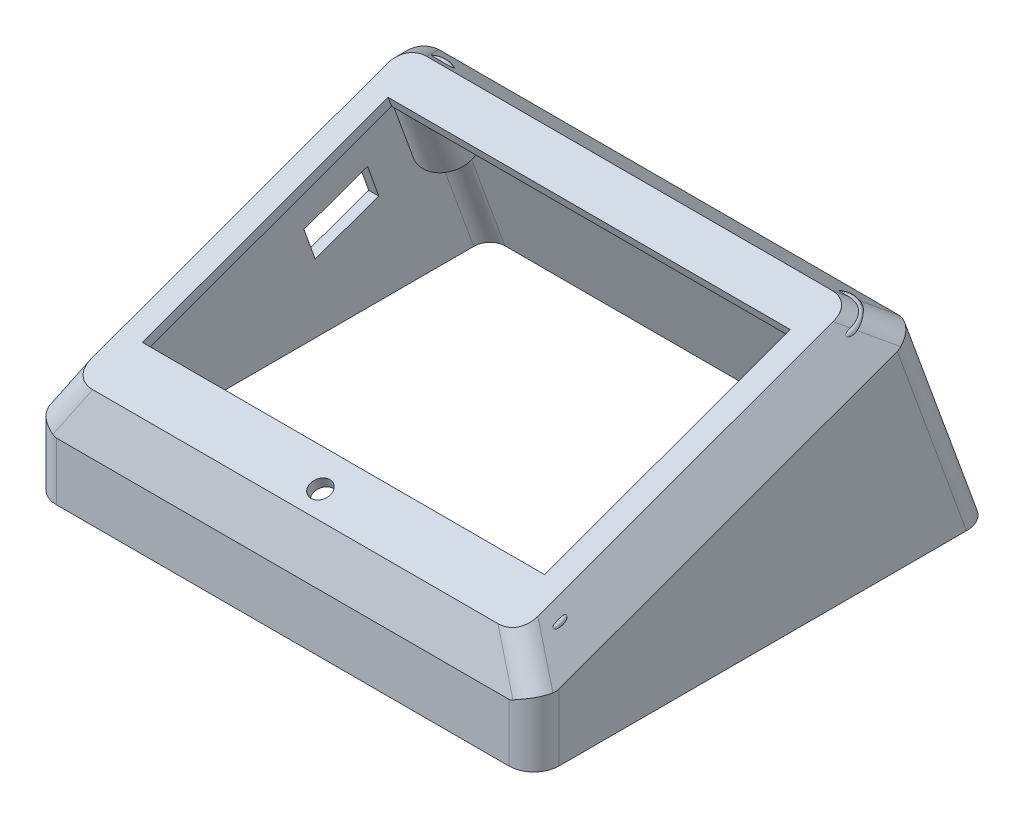
SolidWorks part; units mm, degrees
ref_plane "Front Plane" through (0, 0, 0) normal (0, 0, 1) x (1, 0, 0)
ref_plane "Top Plane" through (0, 0, 0) normal (0, 1, 0) x (1, 0, 0)
ref_plane "Right Plane" through (0, 0, 0) normal (1, 0, 0) x (0, 0, -1)
sketch "Sketch2" plane through (0, 0, 0) normal (1, 0, 0) x (0, 0, -1)
  line L0 (-74.2357, 0) -> (-74.2357, 20)
  line L1 (55, 0) -> (-55, 0) construction
  line L2 (-74.2357, 20) -> (0, 47.0196)
  line L3 (0, 55) -> (0, -55) construction
  line L4 (0, 47.0196) -> (17.1137, 0)
  line L5 (17.1137, 0) -> (-74.2357, 0)
  dimension "D1" = 79
  dimension "D2" = 20
  dimension "D3" = 110
extrude "Boss-Extrude1" add sketch "Sketch2" along normal blind 50 and the other way blind 50
chamfer "Chamfer3" distance 8 angle 35 3 edges at (50, 33.5098, 37.1179) (0, 47.0196, 0) (-50, 33.5098, 37.1179) first distance on face at (50, 16.7549, 32.8394) first distance on face at (0, 23.5098, -8.5569) first distance on face at (-50, 16.7549, 32.8394)
chamfer "Chamfer4" distance 8.5 angle 15 1 edges at (0, 20, 74.2357) first distance on face at (0, 10.4955, 74.2357)
fillet "Fillet7" radius 5 8 edges at (-50, 19.751, -9.9249) (50, 19.751, -9.9249) (-50, 5.7433, 74.2357) (50, 5.7433, 74.2357) (-47.1992, 42.3029, 1.2638) (-47.1948, 16.2093, 72.9739) (47.1992, 42.3029, 1.2638) (47.1948, 16.2093, 72.9739)
shell "Shell1" thickness 2 removed face at (0, 0, 28.6246)
sketch "Sketch5" plane through (0, 39.64, 14.4278) normal (0, -0.9397, -0.342) x (1, 0, 0)
  line L1 (-39.5428, -7.8328) -> (41.3984, -7.8328) construction
  line L2 (-39.5428, -7.8328) -> (-39.5428, 54.064) construction
  line L3 (-39.5428, 54.064) -> (41.3984, 54.064) construction
  line L4 (41.3984, -7.8328) -> (41.3984, 54.064) construction
  circle A0 centre (-39.5428, -7.8328) radius 3
  circle A1 centre (-39.5428, -7.8328) radius 5
  circle A2 centre (-39.5428, 54.064) radius 3
  circle A3 centre (-39.5428, 54.064) radius 5
  circle A4 centre (41.3984, 54.064) radius 3
  circle A5 centre (41.3984, 54.064) radius 5
  circle A6 centre (41.3984, -7.8328) radius 3
  circle A7 centre (41.3984, -7.8328) radius 5
  point P9 (-38.7836, 54.1244)
  point P12 (41.8307, 54.1244)
  point P15 (41.4643, -8.0509)
  dimension "D1" = 6
  dimension "D2" = 2
extrude "Boss-Extrude2" add sketch "Sketch5" along normal blind 14.6 from surface starting at face at (0, 31.1317, 37.8039)
sketch "Sketch3" plane through (0, 41.5193, 15.1118) normal (0, 0.9397, 0.342) x (1, 0, 0)
  line L0 (0, -24.807) -> (0, 24.807) construction
  line L1 (40, -50.02) -> (-40, -50.02)
  line L2 (40, -50.02) -> (40, 1.98)
  line L3 (40, 1.98) -> (-40, 1.98)
  line L4 (-40, -50.02) -> (-40, 1.98)
  line L5 (40, -50.02) -> (-40, 1.98) construction
  line L6 (40, 1.98) -> (-40, -50.02) construction
  line L8 (40.3026, 10.48) -> (-40.3026, 10.48) construction
  circle A0 centre (0.9437, -55.91) radius 2
  point P0 (0, -24.02)
  point P9 (0.9437, -55.6581)
  dimension "D3" = 8.5
  dimension "D1" = 80
  dimension "D2" = 52
extrude "Cut-Extrude1" cut sketch "Sketch3" against normal up to surface (2 mm away) up to face at (0.2678, 28.9184, 43.8851)
sketch "Sketch4" plane through (0, 5.5002, -15.1118) normal (0, 0.342, -0.9397) x (-1, 0, 0)
  line L0 (45, 36.184) -> (-45, 36.184) construction
  line L1 (-8.9, 19.184) -> (4.1, 19.184)
  line L2 (-8.9, 19.184) -> (-8.9, 26.184)
  line L3 (-8.9, 26.184) -> (4.1, 26.184)
  line L4 (4.1, 19.184) -> (4.1, 26.184)
  line L5 (-45, 36.184) -> (-45, -5.8532) construction
  line L7 (-21, 22.184) -> (-11.8, 22.184)
  line L8 (-21, 22.184) -> (-21, 25.684)
  line L9 (-21, 25.684) -> (-11.8, 25.684)
  line L10 (-11.8, 22.184) -> (-11.8, 25.684)
  line L11 (13.1, 23.184) -> (7.1, 23.184)
  line L12 (13.1, 23.184) -> (13.1, 26.184)
  line L13 (13.1, 26.184) -> (7.1, 26.184)
  line L14 (7.1, 23.184) -> (7.1, 26.184)
  dimension "D1" = 9.2
  dimension "D2" = 2.9
  dimension "D3" = 3
  dimension "D4" = 10
  dimension "D5" = 7
  dimension "D6" = 13
  dimension "D7" = 24
  dimension "D8" = 3.5
  dimension "D9" = 10.5
  dimension "D10" = 10
  dimension "D11" = 3
  dimension "D12" = 6
extrude "Cut-Extrude2" cut sketch "Sketch4" against normal up to surface (2 mm away) up to face at (0, 19.1127, -8.0289)
fillet "Fillet8" radius 1.25 4 edges at (21, 26.0043, -6.5848) (21, 29.2933, -5.3877) (11.8, 29.2933, -5.3877) (11.8, 26.0043, -6.5848)
fillet "Fillet10" radius 1 1 edges at (44.6918, 43.6057, 3.5321)
fillet "Fillet11" radius 0.9 1 edges at (-39.6055, 44.0289, 2.3693)
fillet "Fillet12" radius 0.8 1 edges at (46.3984, 21.149, 65.2313)
sketch "Sketch7" plane through (-50, 0, 0) normal (-1, 0, 0) x (0, 0, 1)
  line L0 (19.7624, 13.6031) -> (7.1064, 18.1126)
  line L1 (7.1064, 18.1126) -> (9.3244, 24.3375)
  line L2 (19.7624, 13.6031) -> (21.9804, 19.828)
  line L4 (21.9804, 19.828) -> (9.3244, 24.3375)
extrude "Cut-Extrude3" cut sketch "Sketch7" against normal up to surface (2 mm away) up to face at (-48, 12.4587, 32.1063)
